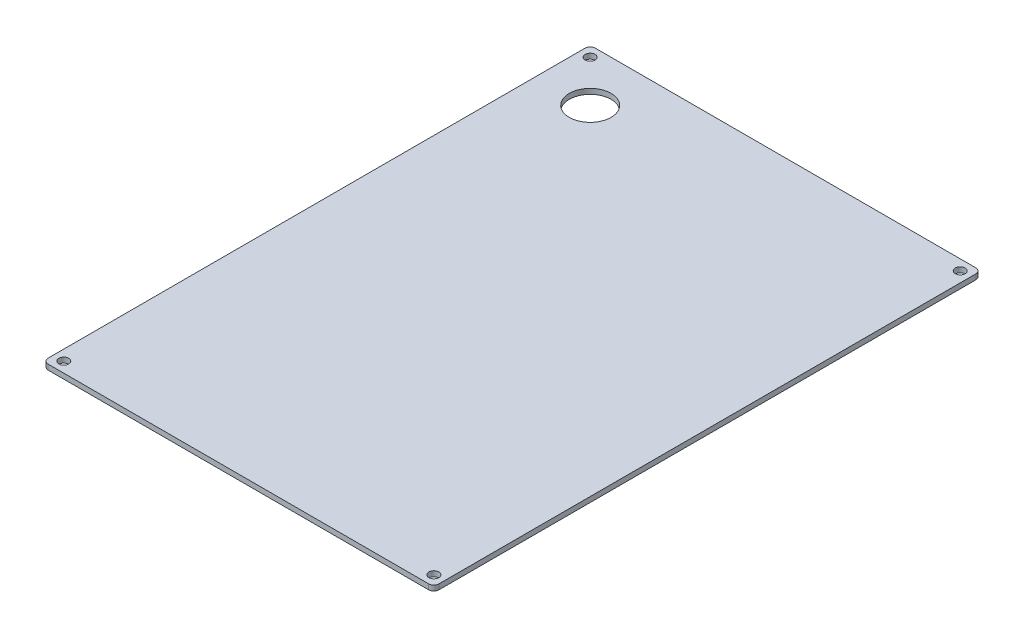
SolidWorks part; units mm, degrees
ref_plane "Front Plane" through (0, 0, 0) normal (0, 0, 1) x (1, 0, 0)
ref_plane "Top Plane" through (0, 0, 0) normal (0, 1, 0) x (1, 0, 0)
ref_plane "Right Plane" through (0, 0, 0) normal (1, 0, 0) x (0, 0, -1)
sketch "Sketch1" plane through (0, 0, 0) normal (0, 1, 0) x (1, 0, 0)
  line L1 (0, 0) -> (150, 0)
  line L2 (0, 0) -> (0, 210)
  line L3 (0, 210) -> (150, 210)
  line L4 (150, 0) -> (150, 210)
  dimension "D1" = 150
  dimension "D2" = 210
extrude "Boss-Extrude1" add sketch "Sketch1" along normal blind 2
sketch "Sketch2" plane through (0, 2, 0) normal (0, 1, 0) x (1, 0, 0)
  line L0 (4, 210) -> (4, 206) construction
  line L1 (150, 210) -> (0, 210) construction
  line L2 (4, 206) -> (0, 206) construction
  line L3 (0, 210) -> (0, 0) construction
  line L4 (75, 210) -> (75, 0) construction
  line L5 (0, 0) -> (150, 0) construction
  line L6 (0, 105) -> (150, 105) construction
  line L7 (150, 0) -> (150, 210) construction
  line L8 (146, 206) -> (150, 206) construction
  line L9 (146, 210) -> (146, 206) construction
  line L10 (146, 0) -> (146, 4) construction
  line L11 (146, 4) -> (150, 4) construction
  line L12 (4, 4) -> (0, 4) construction
  line L13 (4, 0) -> (4, 4) construction
  line L14 (140, 10) -> (140, 0) construction
  line L15 (140, 10) -> (150, 10) construction
  line L16 (0, 190) -> (20, 190) construction
  line L17 (20, 190) -> (20, 210) construction
  circle A0 centre (4, 206) radius 1.9
  circle A1 centre (146, 206) radius 1.9
  circle A2 centre (146, 4) radius 1.9
  circle A3 centre (4, 4) radius 1.9
  circle A5 centre (20, 190) radius 8
  dimension "D2" = 3.8
  dimension "D8" = 16
  dimension "D1" = 4
  dimension "D3" = 10
  dimension "D4" = 10
  dimension "D6" = 20
  dimension "D7" = 20
extrude "Cut-Extrude1" cut sketch "Sketch2" against normal blind 10
fillet "Fillet1" radius 2 4 edges at (0, 1, 0) (150, 1, 0) (150, 1, -210) (0, 1, -210)
